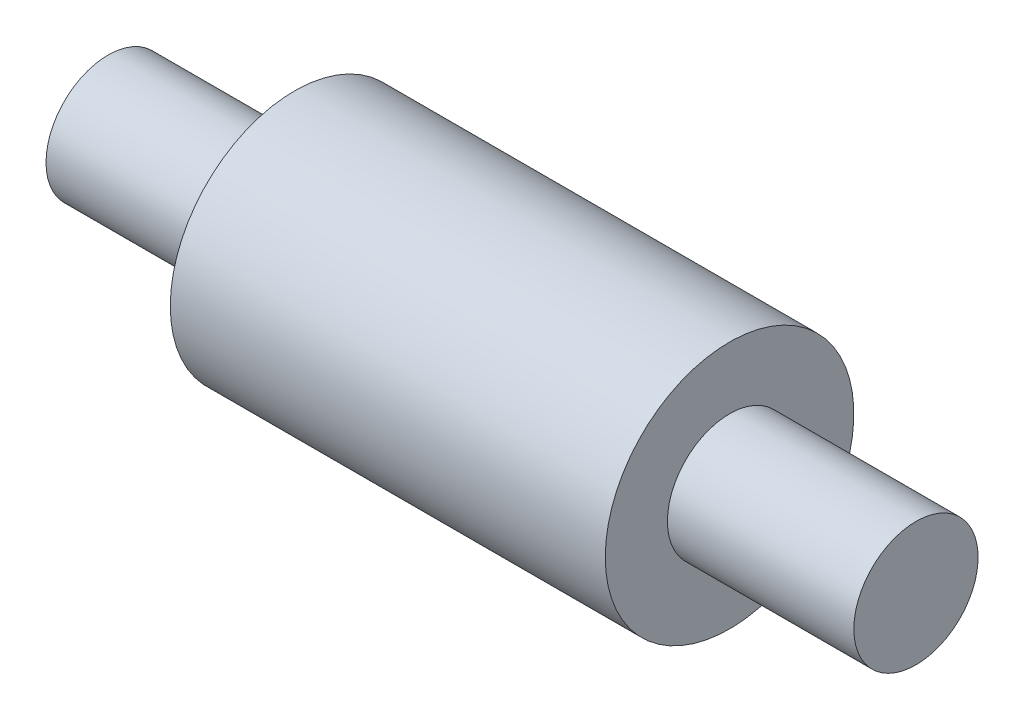
SolidWorks part; units mm, degrees
material "201 Annealed Stainless Steel (SS)"
ref_plane "Front Plane" through (0, 0, 0) normal (0, 0, 1) x (1, 0, 0)
ref_plane "Top Plane" through (0, 0, 0) normal (0, 1, 0) x (1, 0, 0)
ref_plane "Right Plane" through (0, 0, 0) normal (1, 0, 0) x (0, 0, -1)
sketch "Sketch1" plane through (0, 0, 0) normal (0, 0, 1) x (1, 0, 0)
  line L0 (-58.4182, 0) -> (109.1587, 0) construction
  line L1 (0, 0) -> (0, 10)
  line L2 (0, 10) -> (30, 10)
  line L3 (30, 10) -> (30, 20)
  line L4 (30, 20) -> (100, 20)
  line L5 (100, 20) -> (100, 10)
  line L6 (100, 10) -> (130, 10)
  line L7 (130, 10) -> (130, 0)
  line L8 (130, 0) -> (0, 0)
revolve "Revolve2" add sketch "Sketch1" angle 360 about L0
